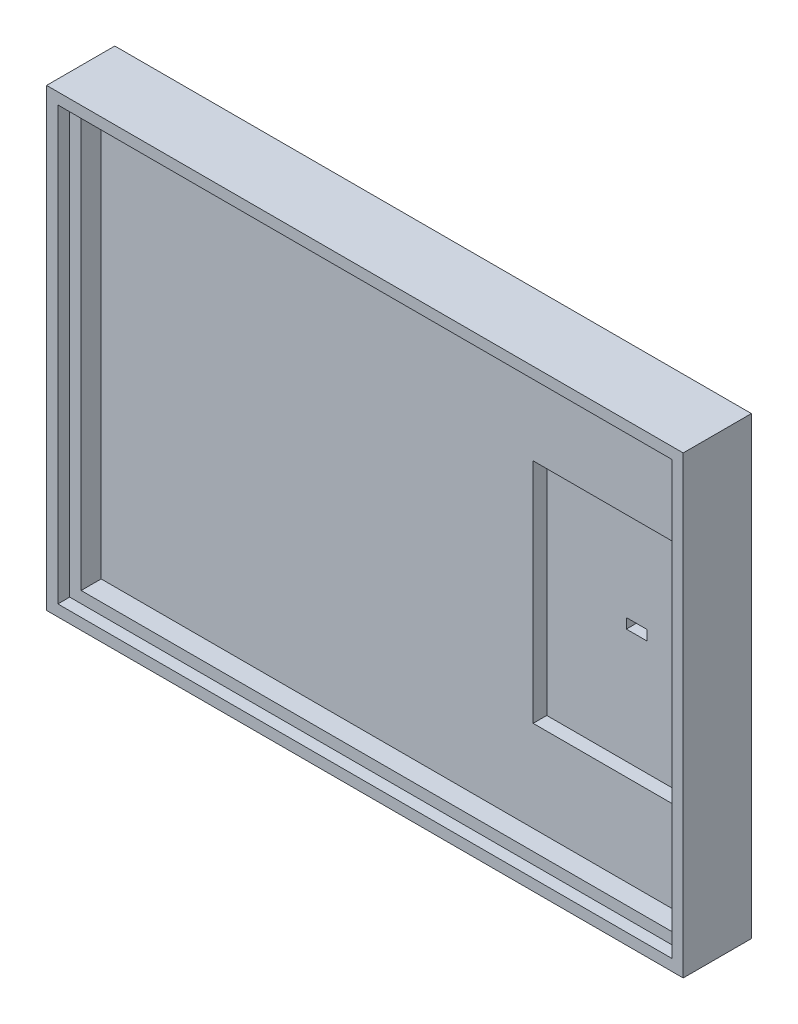
SolidWorks part; units mm, degrees
material "ABS"
ref_plane "Plan de face" through (0, 0, 0) normal (0, 0, 1) x (1, 0, 0)
ref_plane "Plan de dessus" through (0, 0, 0) normal (0, 1, 0) x (1, 0, 0)
ref_plane "Plan de droite" through (0, 0, 0) normal (1, 0, 0) x (0, 0, -1)
sketch "Esquisse1" plane through (0, 0, 0) normal (0, 0, 1) x (1, 0, 0)
  line L1 (-92.4209, 24.1693) -> (47.5791, 24.1693)
  line L2 (-92.4209, 24.1693) -> (-92.4209, -75.8307)
  line L3 (-92.4209, -75.8307) -> (47.5791, -75.8307)
  line L4 (47.5791, 24.1693) -> (47.5791, -75.8307)
  line L5 (-87.4209, 19.1693) -> (42.5791, 19.1693)
  line L6 (-87.4209, 19.1693) -> (-87.4209, -70.8307)
  line L7 (-87.4209, -70.8307) -> (42.5791, -70.8307)
  line L8 (42.5791, 19.1693) -> (42.5791, -70.8307)
  dimension "D1" = 140
  dimension "D2" = 100
  dimension "D3" = 5
  dimension "D4" = 5
  dimension "D5" = 5
  dimension "D6" = 5
extrude "Boss.-Extru.1" add sketch "Esquisse1" along normal blind 15
sketch "Esquisse2" plane through (0, 0, 15) normal (0, 0, 1) x (1, 0, 0)
  line L0 (42.5791, -70.8307) -> (42.5791, 19.1693) construction
  line L1 (-87.4209, 19.1693) -> (42.5791, 19.1693)
  line L2 (-87.4209, 19.1693) -> (-87.4209, -70.8307)
  line L3 (-87.4209, -70.8307) -> (42.5791, -70.8307)
  line L4 (42.5791, 19.1693) -> (42.5791, -70.8307)
  line L5 (-87.4209, 19.1693) -> (-87.4209, -70.8307) construction
  line L6 (42.5791, 19.1693) -> (-87.4209, 19.1693) construction
  line L7 (-87.4209, -70.8307) -> (42.5791, -70.8307) construction
  line L9 (-89.9409, 21.6893) -> (45.0991, 21.6893)
  line L10 (-89.9409, 21.6893) -> (-89.9409, -73.3507)
  line L11 (-89.9409, -73.3507) -> (45.0991, -73.3507)
  line L12 (45.0991, 21.6893) -> (45.0991, -73.3507)
  line L16 (-92.4209, -75.8307) -> (47.5791, -75.8307) construction
  line L17 (47.5791, -75.8307) -> (47.5791, 24.1693) construction
  line L18 (47.5791, 24.1693) -> (-92.4209, 24.1693) construction
  line L19 (-92.4209, 24.1693) -> (-92.4209, -75.8307) construction
  dimension "D1" = 0
  dimension "D2" = 0
  dimension "D3" = 0
  dimension "D4" = 0
  dimension "D5" = 2.48
  dimension "D6" = 2.48
  dimension "D7" = 2.48
  dimension "D8" = 2.48
extrude "Enlèv. mat.-Extru.1" cut sketch "Esquisse2" against normal blind 2.6
sketch "Esquisse3" plane through (47.5791, 0, 0) normal (1, 0, 0) x (0, 0, -1)
  line L0 (-15, -75.8307) -> (0, -75.8307) construction
  line L1 (0, 24.1693) -> (-8, 24.1693)
  line L2 (0, 24.1693) -> (0, -75.8307)
  line L3 (0, -75.8307) -> (-8, -75.8307)
  line L4 (-8, 24.1693) -> (-8, -75.8307)
  dimension "D1" = 8
extrude "Boss.-Extru.2" add sketch "Esquisse3" against normal blind 140
sketch "Esquisse5" plane through (0, 0, 0) normal (0, 0, -1) x (-1, 0, 0)
  text T0 "Smart\r\nForest\r\n 2019" font "Cooper Black" height in points 48
extrude "Enlèv. mat.-Extru.2" cut sketch "Esquisse5" against normal blind 4
sketch "Esquisse6" plane through (0, 0, 0) normal (0, 0, -1) x (-1, 0, 0)
  line L0 (-47.5791, -75.8307) -> (-47.5791, 24.1693) construction
  line L1 (-29.5791, -23.4307) -> (-25.0791, -23.4307)
  line L2 (-29.5791, -23.4307) -> (-29.5791, -25.6307)
  line L3 (-29.5791, -25.6307) -> (-25.0791, -25.6307)
  line L4 (-25.0791, -23.4307) -> (-25.0791, -25.6307)
  line L6 (92.4209, -75.8307) -> (-47.5791, -75.8307) construction
  dimension "D1" = 18
  dimension "D2" = 2.2
  dimension "D3" = 4.5
  dimension "D4" = 50.2
extrude "Enlèv. mat.-Extru.3" cut sketch "Esquisse6" against normal blind 10
sketch "Esquisse7" plane through (0, 0, 8) normal (0, 0, 1) x (1, 0, 0)
  line L1 (7.5791, -0.8307) -> (42.5791, -0.8307)
  line L2 (7.5791, -0.8307) -> (7.5791, -50.8307)
  line L3 (7.5791, -50.8307) -> (42.5791, -50.8307)
  line L4 (42.5791, -0.8307) -> (42.5791, -50.8307)
  line L5 (42.5791, -70.8307) -> (42.5791, 19.1693) construction
  line L6 (42.5791, 19.1693) -> (-87.4209, 19.1693) construction
  dimension "D1" = 35
  dimension "D2" = 50
  dimension "D3" = 0
  dimension "D4" = 20
extrude "Enlèv. mat.-Extru.4" cut sketch "Esquisse7" against normal blind 3
